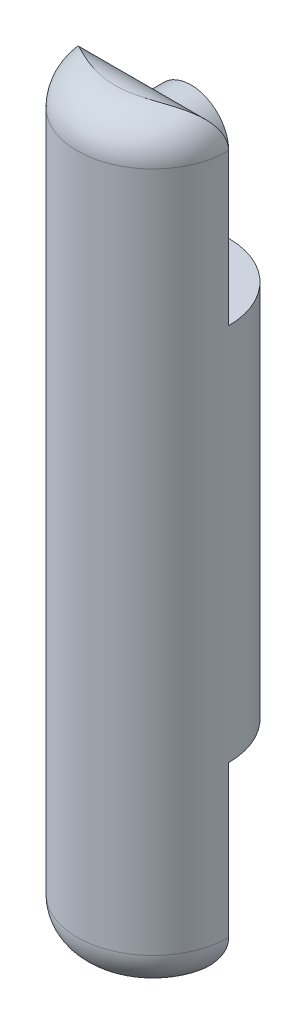
SolidWorks part; units mm, degrees
material "PE Low Density Film"
ref_plane "Front Plane" through (0, 0, 0) normal (0, 0, 1) x (1, 0, 0)
ref_plane "Top Plane" through (0, 0, 0) normal (0, 1, 0) x (1, 0, 0)
ref_plane "Right Plane" through (0, 0, 0) normal (1, 0, 0) x (0, 0, -1)
sketch "Sketch1" plane through (0, 0, 0) normal (0, 1, 0) x (1, 0, 0)
  circle A0 centre (0, 0) radius 10
  dimension "D1" = 20
extrude "Boss-Extrude1" add sketch "Sketch1" along normal blind 100
sketch "Sketch4" plane through (0, 0, 0) normal (0, 0, 1) x (1, 0, 0)
  line L1 (10, 75) -> (-10, 75)
  line L2 (10, 75) -> (10, 100)
  line L3 (10, 100) -> (-10, 100)
  line L4 (-10, 75) -> (-10, 100)
  line L5 (10, 75) -> (-10, 100) construction
  line L6 (10, 100) -> (-10, 75) construction
  point P0 (0, 87.5)
  dimension "D1" = 25
extrude "Cut-Extrude2" cut sketch "Sketch4" against normal blind 10
ref_plane "Plane1" through (0, 50, 0) normal (0, 1, 0) x (1, 0, 0)
sketch "Sketch7" plane through (0, 0, 0) normal (0, 0, 1) x (1, 0, 0)
  line L0 (5.5, 50) -> (-5.5, 50) construction
  circle A0 centre (0, 90.0665) radius 5
  circle A1 centre (0, 9.9335) radius 5
extrude "Boss-Extrude2" add sketch "Sketch7" against normal blind 5
fillet "Fillet7" radius 5 2 edges at (0, 100, 10) (0, 100, 0)
mirror "Mirror3" about plane through (0, 50, 0) normal (0, 1, 0) of "Cut-Extrude2"
sketch "Sketch9" plane through (0, 0, 0) normal (0, 0, 1) x (1, 0, 0)
  circle A0 centre (0, 9.9335) radius 5
extrude "Cut-Extrude3" cut sketch "Sketch9" along normal blind 5
fillet "Fillet8" radius 5 2 edges at (0, 0, 0) (0, 0, 10)
